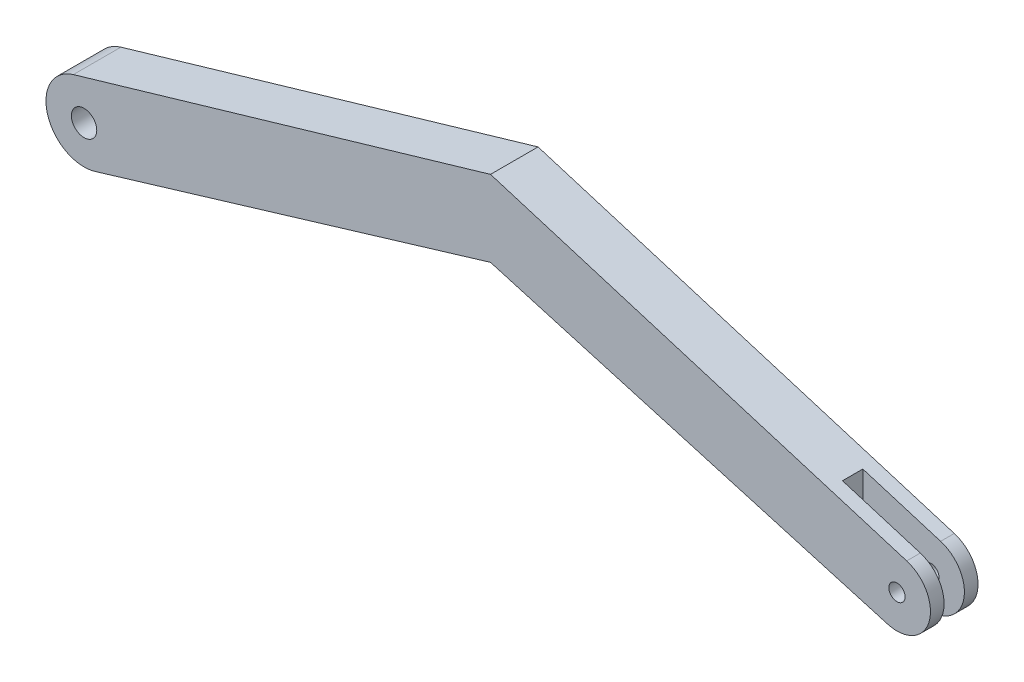
SolidWorks part; units mm, degrees
ref_plane "Front Plane" through (0, 0, 0) normal (0, 0, 1) x (1, 0, 0)
ref_plane "Top Plane" through (0, 0, 0) normal (0, 1, 0) x (1, 0, 0)
ref_plane "Right Plane" through (0, 0, 0) normal (1, 0, 0) x (0, 0, -1)
sketch "Sketch1" plane through (0, 0, 0) normal (0, 0, 1) x (1, 0, 0)
  line L2 (-50.1138, -2.2802) -> (-25.4, 5.1566)
  line L3 (-25.4, 5.1566) -> (-0.5816, -2.0132)
  line L4 (-51.4692, 2.2853) -> (-25.4, 9.9191)
  line L5 (-25.4, 9.9191) -> (0.61, 2.0047)
  circle A0 centre (0, 0) radius 0.508
  circle A1 centre (-50.8, 0) radius 0.7937
  arc A4 (-51.4692, 2.2853) -> (-50.1138, -2.2802) centre (-50.8, 0) ccw
  arc A5 (-0.5816, -2.0132) -> (0.61, 2.0047) centre (0, 0) ccw
  circle A7 centre (-50.8, 0) radius 2.3813 construction
  circle A8 centre (0, 0) radius 2.0955 construction
  point P6 (-50.8, 0)
  point P7 (2.0955, 0)
  point P8 (0, 0)
  point P9 (2.0955, 0)
  point P13 (-29.7511, 0)
  point P19 (-48.4187, 0)
  dimension "D1" = 1.5875
  dimension "D2" = 1.016
  dimension "D3" = 50.8
  dimension "D5" = 4.7625
  dimension "D6" = 25.4
  dimension "D4" = 1.5875
extrude "Boss-Extrude1" add sketch "Sketch1" along normal blind 2.9718 contours A0 A1 | A0 region at (-52.5399, -0.5165, 0) region at (0, 0, 0)
sketch "Sketch2" plane through (0, 0, 0) normal (0, 1, 0) x (1, 0, 0)
  line L0 (-42.8958, 0) -> (-42.8958, -2.9718) construction
  line L1 (-4.2545, -2.1209) -> (4.2841, -2.1209)
  line L2 (-4.2545, -2.1209) -> (-4.2545, -0.8509)
  line L3 (-4.2545, -0.8509) -> (4.2841, -0.8509)
  line L4 (4.2841, -2.1209) -> (4.2841, -0.8509)
  line L5 (-4.2545, -2.1209) -> (4.2841, -0.8509) construction
  line L6 (-4.2545, -0.8509) -> (4.2841, -2.1209) construction
  line L8 (0.0148, -2.9718) -> (0.0148, 0) construction
  line L9 (0.0148, 0) -> (0.0148, -2.9718) construction
  line L10 (2.0955, -2.9718) -> (2.0955, 0) construction
  point P0 (-42.8958, -1.4859)
  point P7 (0.0148, -0.8509)
  point P14 (0.0148, -1.4859)
  point P15 (0.0148, -1.4859)
  dimension "D1" = 1.27
  dimension "D2" = 6.35
extrude "Cut-Extrude1" cut sketch "Sketch2" against normal through all both and the other way through all
extrude "Cut-Extrude3" cut sketch "Sketch1<4>" along normal through all both contours A0
sketch "Sketch1<4>" plane through (0, 0, 0) normal (0, 0, 1) x (1, 0, 0) same geometry as "Sketch1"
